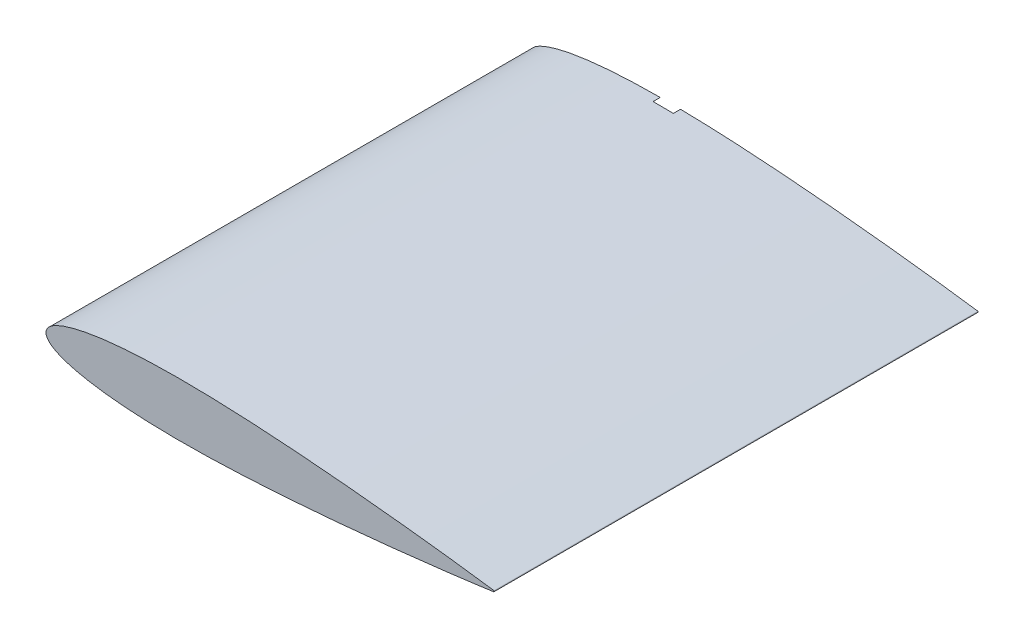
SolidWorks part; units mm, degrees
ref_plane "Front Plane" through (0, 0, 0) normal (0, 0, 1) x (1, 0, 0)
ref_plane "Top Plane" through (0, 0, 0) normal (0, 1, 0) x (1, 0, 0)
ref_plane "Right Plane" through (0, 0, 0) normal (1, 0, 0) x (0, 0, -1)
curve "Curve2"
  spline degree 3 poles (0.9995, -0.0017, 0) (1.0002, 0, 0) (0.9995, 0.0017, 0) (0.9972, 0.0015, 0) (0.9944, 0.0021, 0) (0.9903, 0.0026, 0) (0.9851, 0.0033, 0) (0.9787, 0.0042, 0) (0.9713, 0.0052, 0) (0.9627, 0.0064, 0) (0.9531, 0.0077, 0) (0.9424, 0.0091, 0) (0.9307, 0.0106, 0) (0.9179, 0.0122, 0) (0.9042, 0.014, 0) (0.8895, 0.0158, 0) (0.874, 0.0177, 0) (0.8575, 0.0196, 0) (0.8402, 0.0217, 0) (0.8222, 0.0237, 0) (0.8033, 0.0259, 0) (0.7838, 0.028, 0) (0.7636, 0.0302, 0) (0.7428, 0.0324, 0) (0.7214, 0.0345, 0) (0.6995, 0.0367, 0) (0.6772, 0.0388, 0) (0.6544, 0.0409, 0) (0.6313, 0.043, 0) (0.6078, 0.045, 0) (0.5841, 0.0469, 0) (0.5602, 0.0488, 0) (0.5362, 0.0505, 0) (0.5121, 0.0522, 0) (0.4879, 0.0537, 0) (0.4638, 0.0551, 0) (0.4398, 0.0563, 0) (0.4159, 0.0574, 0) (0.3922, 0.0583, 0) (0.3688, 0.0591, 0) (0.3456, 0.0596, 0) (0.3228, 0.0599, 0) (0.3005, 0.0601, 0) (0.2786, 0.06, 0) (0.2572, 0.0596, 0) (0.2364, 0.0591, 0) (0.2162, 0.0583, 0) (0.1966, 0.0572, 0) (0.1778, 0.056, 0) (0.1597, 0.0544, 0) (0.1425, 0.0527, 0) (0.126, 0.0507, 0) (0.1104, 0.0486, 0) (0.0958, 0.0462, 0) (0.0821, 0.0436, 0) (0.0693, 0.0408, 0) (0.0576, 0.0378, 0) (0.0468, 0.0347, 0) (0.0372, 0.0313, 0) (0.0286, 0.0279, 0) (0.0211, 0.0243, 0) (0.0147, 0.0206, 0) (0.0094, 0.0167, 0) (0.0053, 0.0128, 0) (0.0023, 0.0087, 0) (0.0004, 0.0044, 0) (-0.0002, 0, 0) (0.0004, -0.0044, 0) (0.0023, -0.0087, 0) (0.0053, -0.0128, 0) (0.0094, -0.0167, 0) (0.0147, -0.0206, 0) (0.0211, -0.0243, 0) (0.0286, -0.0279, 0) (0.0372, -0.0313, 0) (0.0468, -0.0347, 0) (0.0576, -0.0378, 0) (0.0693, -0.0408, 0) (0.0821, -0.0436, 0) (0.0958, -0.0462, 0) (0.1104, -0.0486, 0) (0.126, -0.0507, 0) (0.1425, -0.0527, 0) (0.1597, -0.0544, 0) (0.1778, -0.056, 0) (0.1966, -0.0572, 0) (0.2162, -0.0583, 0) (0.2364, -0.0591, 0) (0.2572, -0.0596, 0) (0.2786, -0.06, 0) (0.3005, -0.0601, 0) (0.3228, -0.0599, 0) (0.3456, -0.0596, 0) (0.3688, -0.0591, 0) (0.3922, -0.0583, 0) (0.4159, -0.0574, 0) (0.4398, -0.0563, 0) (0.4638, -0.0551, 0) (0.4879, -0.0537, 0) (0.5121, -0.0522, 0) (0.5362, -0.0505, 0) (0.5602, -0.0488, 0) (0.5841, -0.0469, 0) (0.6078, -0.045, 0) (0.6313, -0.043, 0) (0.6544, -0.0409, 0) (0.6772, -0.0388, 0) (0.6995, -0.0367, 0) (0.7214, -0.0345, 0) (0.7428, -0.0324, 0) (0.7636, -0.0302, 0) (0.7838, -0.028, 0) (0.8033, -0.0259, 0) (0.8222, -0.0237, 0) (0.8402, -0.0217, 0) (0.8575, -0.0196, 0) (0.874, -0.0177, 0) (0.8895, -0.0158, 0) (0.9042, -0.014, 0) (0.9179, -0.0122, 0) (0.9307, -0.0106, 0) (0.9424, -0.0091, 0) (0.9531, -0.0077, 0) (0.9627, -0.0064, 0) (0.9713, -0.0052, 0) (0.9787, -0.0042, 0) (0.9851, -0.0033, 0) (0.9903, -0.0026, 0) (0.9944, -0.0021, 0) (0.9972, -0.0015, 0) (0.9995, -0.0017, 0) (1.0002, 0, 0) (0.9995, 0.0017, 0) knots -0.003024 -0.001583 -0.000717 0 0.000717 0.001583 0.003024 0.005037 0.007616 0.010755 0.014448 0.018684 0.023454 0.028747 0.034549 0.040847 0.047626 0.05487 0.062562 0.070682 0.079213 0.088133 0.097423 0.107059 0.117019 0.12728 0.137818 0.148607 0.159622 0.170839 0.182229 0.193767 0.205424 0.217175 0.22899 0.240844 0.252707 0.264552 0.276352 0.28808 0.299708 0.311209 0.322557 0.333727 0.344692 0.35543 0.365915 0.376124 0.386035 0.395627 0.404879 0.413773 0.422288 0.430409 0.438119 0.445404 0.45225 0.458647 0.464584 0.470056 0.475056 0.479587 0.483651 0.487261 0.49044 0.493225 0.495678 0.497893 0.5 0.502107 0.504322 0.506775 0.50956 0.512739 0.516349 0.520413 0.524944 0.529944 0.535416 0.541353 0.54775 0.554596 0.561881 0.569591 0.577712 0.586227 0.595121 0.604373 0.613965 0.623876 0.634085 0.64457 0.655308 0.666273 0.677443 0.688791 0.700292 0.71192 0.723648 0.735448 0.747293 0.759156 0.77101 0.782825 0.794576 0.806233 0.817771 0.829161 0.840378 0.851393 0.862182 0.87272 0.882981 0.892941 0.902577 0.911867 0.920787 0.929318 0.937438 0.94513 0.952374 0.959153 0.965451 0.971253 0.976546 0.981316 0.985552 0.989245 0.992384 0.994963 0.996976 0.998417 0.999283 1 1.000717 1.001583 1.003024 periodic
sketch "Sketch2" plane through (0, 0, 0) normal (0, 0, 1) x (1, 0, 0)
  spline S1 degree 3 poles (49.9764, -0.0863) (50.0107, 0) (49.9764, 0.0863) (49.8586, 0.0728) (49.7209, 0.1067) (49.5142, 0.129) (49.255, 0.1672) (48.9374, 0.21) (48.5645, 0.2611) (48.1364, 0.3187) (47.6543, 0.383) (47.1192, 0.4535) (46.5325, 0.5298) (45.8956, 0.6114) (45.2098, 0.6979) (44.4768, 0.7889) (43.6983, 0.8838) (42.8762, 0.9822) (42.0123, 1.0836) (41.1086, 1.1875) (40.1674, 1.2934) (39.1907, 1.4008) (38.1809, 1.5092) (37.1403, 1.6179) (36.0713, 1.7267) (34.9765, 1.8348) (33.8584, 1.9418) (32.7196, 2.047) (31.5628, 2.1501) (30.3906, 2.2501) (29.2058, 2.3467) (28.0113, 2.4392) (26.8096, 2.5268) (25.6038, 2.6091) (24.3966, 2.6854) (23.1907, 2.7549) (21.9891, 2.8172) (20.7945, 2.8714) (19.6098, 2.917) (18.4376, 2.9535) (17.2807, 2.9803) (16.1419, 2.9968) (15.0237, 3.0027) (13.9288, 2.9975) (12.8597, 2.9811) (11.8191, 2.9528) (10.8091, 2.913) (9.8323, 2.8612) (8.891, 2.7976) (7.9872, 2.7223) (7.1231, 2.6353) (6.3008, 2.5371) (5.522, 2.4279) (4.7888, 2.308) (4.1026, 2.178) (3.4652, 2.0385) (2.8779, 1.8897) (2.3422, 1.7325) (1.8592, 1.5674) (1.4298, 1.3949) (1.0551, 1.2155) (0.7356, 1.0295) (0.4717, 0.8374) (0.264, 0.6388) (0.113, 0.4331) (0.0206, 0.2193) (-0.0101, 0) (0.0206, -0.2193) (0.113, -0.4331) (0.264, -0.6388) (0.4717, -0.8374) (0.7356, -1.0295) (1.0551, -1.2155) (1.4298, -1.3949) (1.8592, -1.5674) (2.3422, -1.7325) (2.8779, -1.8897) (3.4652, -2.0385) (4.1026, -2.178) (4.7888, -2.308) (5.522, -2.4279) (6.3008, -2.5371) (7.1231, -2.6353) (7.9872, -2.7223) (8.891, -2.7976) (9.8323, -2.8612) (10.8091, -2.913) (11.8191, -2.9528) (12.8597, -2.9811) (13.9288, -2.9975) (15.0237, -3.0027) (16.1419, -2.9968) (17.2807, -2.9803) (18.4376, -2.9535) (19.6098, -2.917) (20.7945, -2.8714) (21.9891, -2.8172) (23.1907, -2.7549) (24.3966, -2.6854) (25.6038, -2.6091) (26.8096, -2.5268) (28.0113, -2.4392) (29.2058, -2.3467) (30.3906, -2.2501) (31.5628, -2.1501) (32.7196, -2.047) (33.8584, -1.9418) (34.9765, -1.8348) (36.0713, -1.7267) (37.1403, -1.6179) (38.1809, -1.5092) (39.1907, -1.4008) (40.1674, -1.2934) (41.1086, -1.1875) (42.0123, -1.0836) (42.8762, -0.9822) (43.6983, -0.8838) (44.4768, -0.7889) (45.2098, -0.6979) (45.8956, -0.6114) (46.5325, -0.5298) (47.1192, -0.4535) (47.6543, -0.383) (48.1364, -0.3187) (48.5645, -0.2611) (48.9374, -0.21) (49.255, -0.1672) (49.5142, -0.129) (49.7209, -0.1067) (49.8586, -0.0728) (49.9764, -0.0863) (50.0107, 0) (49.9764, 0.0863) knots -0.003024 -0.001583 -0.000717 0 0.000717 0.001583 0.003024 0.005037 0.007616 0.010755 0.014448 0.018684 0.023454 0.028747 0.034549 0.040847 0.047626 0.05487 0.062562 0.070682 0.079213 0.088133 0.097423 0.107059 0.117019 0.12728 0.137818 0.148607 0.159622 0.170839 0.182229 0.193767 0.205424 0.217175 0.22899 0.240844 0.252707 0.264552 0.276352 0.28808 0.299708 0.311209 0.322557 0.333727 0.344692 0.35543 0.365915 0.376124 0.386035 0.395627 0.404879 0.413773 0.422288 0.430409 0.438119 0.445404 0.45225 0.458647 0.464584 0.470056 0.475056 0.479587 0.483651 0.487261 0.49044 0.493225 0.495678 0.497893 0.5 0.502107 0.504322 0.506775 0.50956 0.512739 0.516349 0.520413 0.524944 0.529944 0.535416 0.541353 0.54775 0.554596 0.561881 0.569591 0.577712 0.586227 0.595121 0.604373 0.613965 0.623876 0.634085 0.64457 0.655308 0.666273 0.677443 0.688791 0.700292 0.71192 0.723648 0.735448 0.747293 0.759156 0.77101 0.782825 0.794576 0.806233 0.817771 0.829161 0.840378 0.851393 0.862182 0.87272 0.882981 0.892941 0.902577 0.911867 0.920787 0.929318 0.937438 0.94513 0.952374 0.959153 0.965451 0.971253 0.976546 0.981316 0.985552 0.989245 0.992384 0.994963 0.996976 0.998417 0.999283 1 1.000717 1.001583 1.003024 only from (50, 0) to (50, 0)
extrude "Boss-Extrude1" add sketch "Sketch2" along normal blind 54
sketch "Sketch3" plane through (0, 0, 0) normal (0, 0, -1) x (-1, 0, 0)
  circle A0 centre (-3.6587, 0) radius 0.75
  circle A1 centre (-15.6587, 0) radius 3.2
  circle A2 centre (-27.6587, 0) radius 0.75
  dimension "D3" = 6.4
  dimension "D4" = 1.5
  dimension "D5" = 1.5
  dimension "D1" = 12
  dimension "D2" = 12
extrude "Cut-Extrude1" cut sketch "Sketch3" against normal blind 0.8
sketch "Sketch4" plane through (0, 0, 0.8) normal (0, 0, -1) x (-1, 0, 0)
  circle A0 centre (-15.6587, 0) radius 2.25
  arc A1 (-14.5449, -2.9999) -> (-14.5449, 2.9999) centre (-15.6587, 0) ccw construction
  dimension "D2" = 4.5
extrude "Cut-Extrude2" cut sketch "Sketch4" against normal blind 2
other "Move Face1" flip direction yes face at (2.9087, 0, 0.8) face at (26.9087, 0, 0.8) offset 9 parameters "D1"=9
sketch "Sketch5" plane through (0, 0, 0) normal (0, 0, 1) x (1, 0, 0)
  circle A4 centre (25.6587, 0) radius 0.5
  circle A6 centre (23.6587, 0) radius 0.5
  circle A10 centre (7.6587, 0) radius 0.5
  circle A12 centre (5.6587, 0) radius 0.5
  circle A20 centre (25.6587, 0) radius 0.75
  circle A21 centre (23.6587, 0) radius 0.75
  circle A22 centre (7.6587, 0) radius 0.75
  circle A23 centre (5.6587, 0) radius 0.75
  dimension "D1" = 1.5
  dimension "D2" = 1.5
  dimension "D3" = 1.5
  dimension "D4" = 1.5
extrude "Cut-Extrude3" cut sketch "Sketch5" along normal blind 10 contours A23 | A22 | A21 | A20
